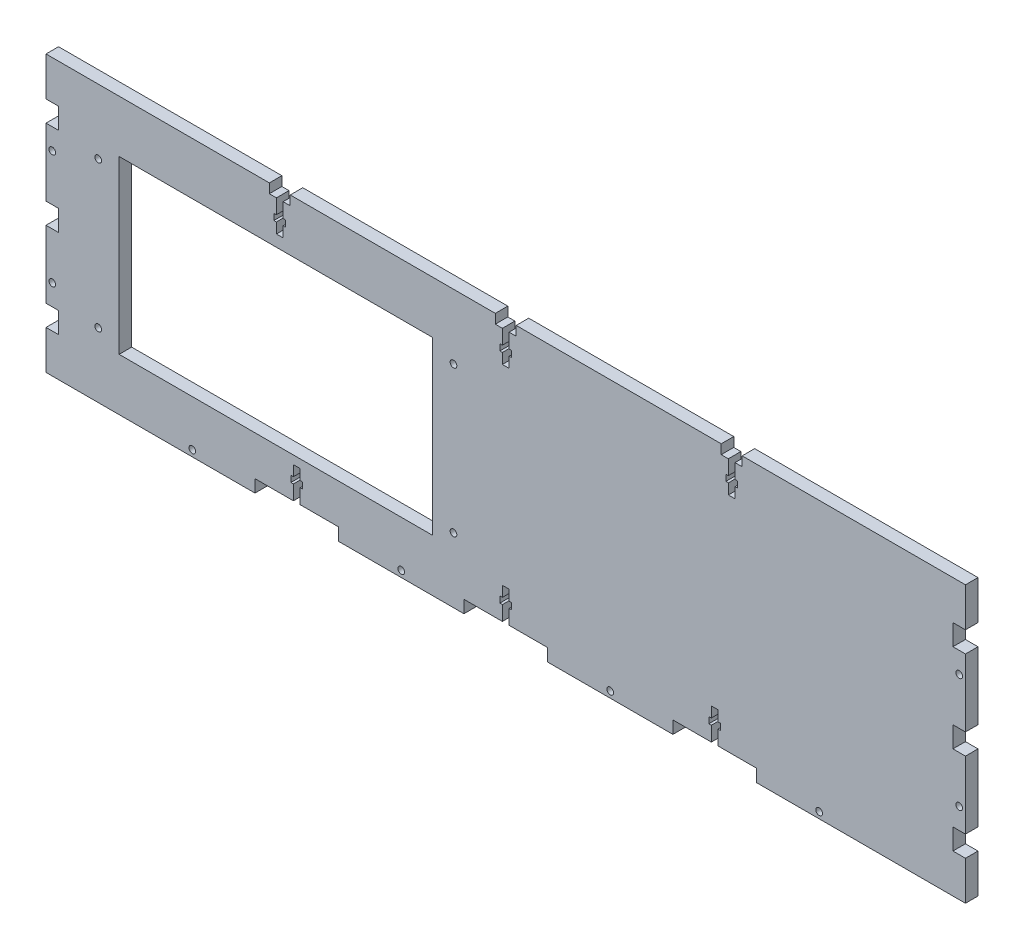
SolidWorks part; units mm, degrees
ref_plane "Front Plane" through (0, 0, 0) normal (0, 0, 1) x (1, 0, 0)
ref_plane "Top Plane" through (0, 0, 0) normal (0, 1, 0) x (1, 0, 0)
ref_plane "Right Plane" through (0, 0, 0) normal (1, 0, 0) x (0, 0, -1)
sketch "Sketch1" plane through (0, 0, 0) normal (0, 0, 1) x (1, 0, 0)
  line L1 (-220, -66) -> (220, -66)
  line L2 (-220, -66) -> (-220, 66)
  line L3 (-220, 66) -> (220, 66)
  line L4 (220, -66) -> (220, 66)
  line L5 (-220, -66) -> (220, 66) construction
  line L6 (-220, 66) -> (220, -66) construction
  point P0 (0, 0)
  dimension "D1" = 440
  dimension "D2" = 132
extrude "Boss-Extrude1" add sketch "Sketch1" along normal blind 6
sketch "Sketch2" plane through (0, 0, 0) normal (0, 0, -1) x (-1, 0, 0)
  line L0 (220, 47.3321) -> (220, 37.3321) construction
  line L1 (220, 37.3321) -> (214, 37.3321) construction
  line L2 (214, 37.3321) -> (214, 47.3321) construction
  line L3 (214, 47.3321) -> (220, 47.3321) construction
  line L12 (220, -37.3321) -> (220, -47.3321) construction
  line L13 (220, -47.3321) -> (214, -47.3321) construction
  line L14 (214, -47.3321) -> (214, -37.3321) construction
  line L15 (214, -37.3321) -> (220, -37.3321) construction
  line L16 (220, 47.3321) -> (220, 37.3321)
  line L17 (220, 37.3321) -> (214, 37.3321)
  line L18 (214, 37.3321) -> (214, 47.3321)
  line L19 (214, 47.3321) -> (220, 47.3321)
  line L20 (220, -37.3321) -> (220, -47.3321)
  line L21 (220, -47.3321) -> (214, -47.3321)
  line L22 (214, -47.3321) -> (214, -37.3321)
  line L23 (214, -37.3321) -> (220, -37.3321)
  line L24 (-214, -37.3321) -> (-214, -47.3321) construction
  line L25 (-214, -47.3321) -> (-220, -47.3321) construction
  line L26 (-220, -47.3321) -> (-220, -37.3321) construction
  line L27 (-220, -37.3321) -> (-214, -37.3321) construction
  line L28 (-214, 47.3321) -> (-214, 37.3321) construction
  line L29 (-214, 37.3321) -> (-220, 37.3321) construction
  line L30 (-220, 37.3321) -> (-220, 47.3321) construction
  line L31 (-220, 47.3321) -> (-214, 47.3321) construction
  line L32 (-214, -37.3321) -> (-214, -47.3321)
  line L33 (-214, -47.3321) -> (-220, -47.3321)
  line L34 (-220, -47.3321) -> (-220, -37.3321)
  line L35 (-220, -37.3321) -> (-214, -37.3321)
  line L36 (-214, 47.3321) -> (-214, 37.3321)
  line L37 (-214, 37.3321) -> (-220, 37.3321)
  line L38 (-220, 37.3321) -> (-220, 47.3321)
  line L39 (-220, 47.3321) -> (-214, 47.3321)
  line L44 (220, -5) -> (220, 5)
  line L45 (214, -5) -> (220, -5)
  line L46 (214, 5) -> (214, -5)
  line L47 (220, 5) -> (214, 5)
  line L48 (220, -5) -> (220, 5)
  line L49 (214, -5) -> (220, -5)
  line L50 (214, 5) -> (214, -5)
  line L51 (220, 5) -> (214, 5)
  line L52 (-214, -5) -> (-214, 5)
  line L53 (-220, -5) -> (-214, -5)
  line L54 (-220, 5) -> (-220, -5)
  line L55 (-214, 5) -> (-220, 5)
  line L56 (-214, -5) -> (-214, 5)
  line L57 (-220, -5) -> (-214, -5)
  line L58 (-220, 5) -> (-220, -5)
  line L59 (-214, 5) -> (-220, 5)
  circle A0 centre (217, 27.3321) radius 1.6 construction
  circle A1 centre (217, -27.3321) radius 1.6 construction
  circle A2 centre (-217, 27.3321) radius 1.6 construction
  circle A3 centre (-217, -27.3321) radius 1.6 construction
  circle A4 centre (217, 27.3321) radius 1.6
  circle A5 centre (217, -27.3321) radius 1.6
  circle A6 centre (-217, 27.3321) radius 1.6
  circle A7 centre (-217, -27.3321) radius 1.6
  dimension "D2" = 0
  dimension "D3" = 0
extrude "Cut-Extrude1" cut sketch "Sketch2" against normal up to next
sketch "Sketch3" plane through (0, 0, 0) normal (0, 0, -1) x (-1, 0, 0)
  circle A0 centre (-150, -63) radius 1.6 construction
  circle A1 centre (-50, -63) radius 1.6 construction
  circle A2 centre (50, -63) radius 1.6 construction
  circle A3 centre (150, -63) radius 1.6 construction
  circle A4 centre (-150, -63) radius 1.6
  circle A5 centre (-50, -63) radius 1.6
  circle A6 centre (50, -63) radius 1.6
  circle A7 centre (150, -63) radius 1.6
extrude "Cut-Extrude2" cut sketch "Sketch3" against normal up to next
sketch "Sketch4" plane through (0, 0, 0) normal (0, 0, -1) x (-1, 0, 0)
  line L0 (80, -66) -> (120, -66) construction
  line L1 (120, -66) -> (120, -60) construction
  line L2 (120, -60) -> (80, -60) construction
  line L3 (80, -60) -> (80, -66) construction
  line L4 (-20, -66) -> (20, -66) construction
  line L5 (20, -66) -> (20, -60) construction
  line L6 (20, -60) -> (-20, -60) construction
  line L7 (-20, -60) -> (-20, -66) construction
  line L8 (-120, -66) -> (-80, -66) construction
  line L9 (-80, -66) -> (-80, -60) construction
  line L10 (-80, -60) -> (-120, -60) construction
  line L11 (-120, -60) -> (-120, -66) construction
  line L12 (80, -66) -> (120, -66)
  line L13 (120, -66) -> (120, -60)
  line L14 (120, -60) -> (80, -60)
  line L15 (80, -60) -> (80, -66)
  line L16 (-20, -66) -> (20, -66)
  line L17 (20, -66) -> (20, -60)
  line L18 (20, -60) -> (-20, -60)
  line L19 (-20, -60) -> (-20, -66)
  line L20 (-120, -66) -> (-80, -66)
  line L21 (-80, -66) -> (-80, -60)
  line L22 (-80, -60) -> (-120, -60)
  line L23 (-120, -60) -> (-120, -66)
extrude "Cut-Extrude3" cut sketch "Sketch4" against normal up to next
sketch "Sketch5" plane through (0, 66, 0) normal (0, 1, 0) x (1, 0, 0)
  line L0 (220, 0) -> (-220, 0) construction
  line L1 (-113.125, -6) -> (-103.125, -6)
  line L2 (-113.125, -6) -> (-113.125, 0)
  line L3 (-113.125, 0) -> (-103.125, 0)
  line L4 (-103.125, -6) -> (-103.125, 0)
  line L5 (-113.125, -6) -> (-103.125, 0) construction
  line L6 (-113.125, 0) -> (-103.125, -6) construction
  line L7 (-103.125, -6) -> (-103.125, 0) construction
  line L8 (5, -6) -> (5, 0) construction
  line L9 (-5, -6) -> (5, -6)
  line L10 (-5, -6) -> (-5, 0)
  line L11 (-5, 0) -> (5, 0)
  line L12 (5, -6) -> (5, 0)
  line L13 (-5, -6) -> (5, 0) construction
  line L14 (-5, 0) -> (5, -6) construction
  line L15 (113.125, -6) -> (113.125, 0) construction
  line L16 (103.125, -6) -> (113.125, -6)
  line L17 (103.125, -6) -> (103.125, 0)
  line L18 (103.125, 0) -> (113.125, 0)
  line L19 (113.125, -6) -> (113.125, 0)
  line L20 (103.125, -6) -> (113.125, 0) construction
  line L21 (103.125, 0) -> (113.125, -6) construction
  point P0 (-108.125, -3)
  point P10 (0, -3)
  point P18 (108.125, -3)
extrude "Cut-Extrude4" cut sketch "Sketch5" against normal blind 4.5
sketch "Sketch6" plane through (0, 0, 0) normal (0, 0, -1) x (-1, 0, 0)
  line L0 (-108.125, 61.5) -> (-108.125, 46.5) construction
  line L1 (-113.125, 61.5) -> (-103.125, 61.5) construction
  line L2 (-109.725, 61.5) -> (-109.725, 54.5)
  line L3 (-106.525, 61.5) -> (-106.525, 54.5)
  line L4 (-109.725, 61.5) -> (-106.525, 61.5)
  line L5 (-109.725, 46.5) -> (-106.525, 46.5)
  line L6 (-106.525, 51.5) -> (-105.325, 51.5)
  line L7 (-110.925, 54.5) -> (-109.725, 54.5)
  line L8 (-110.925, 54.5) -> (-110.925, 51.5)
  line L9 (-110.925, 51.5) -> (-109.725, 51.5)
  line L10 (-105.325, 54.5) -> (-105.325, 51.5)
  line L11 (-110.925, 54.5) -> (-105.325, 51.5) construction
  line L12 (-110.925, 51.5) -> (-105.325, 54.5) construction
  line L13 (-106.525, 51.5) -> (-106.525, 46.5)
  line L14 (-106.525, 61.5) -> (-106.525, 46.5) construction
  line L15 (-109.725, 51.5) -> (-109.725, 46.5)
  line L16 (-109.725, 61.5) -> (-109.725, 46.5) construction
  line L17 (-106.525, 54.5) -> (-105.325, 54.5)
  line L18 (-1.595, 61.5) -> (-1.595, 54.5)
  line L19 (1.605, 61.5) -> (1.605, 54.5)
  line L20 (-1.595, 61.5) -> (1.605, 61.5)
  line L21 (-1.595, 46.5) -> (1.605, 46.5)
  line L22 (1.605, 51.5) -> (2.805, 51.5)
  line L23 (-2.795, 54.5) -> (-1.595, 54.5)
  line L24 (-2.795, 54.5) -> (-2.795, 51.5)
  line L25 (-2.795, 51.5) -> (-1.595, 51.5)
  line L26 (2.805, 54.5) -> (2.805, 51.5)
  line L27 (1.605, 51.5) -> (1.605, 46.5)
  line L28 (-1.595, 51.5) -> (-1.595, 46.5)
  line L29 (1.605, 54.5) -> (2.805, 54.5)
  line L30 (0.005, 61.5) -> (0.005, 46.5) construction
  line L31 (-2.795, 54.5) -> (2.805, 51.5) construction
  line L32 (-2.795, 51.5) -> (2.805, 54.5) construction
  line L33 (106.535, 61.5) -> (106.535, 54.5)
  line L34 (109.735, 61.5) -> (109.735, 54.5)
  line L35 (106.535, 61.5) -> (109.735, 61.5)
  line L36 (106.535, 46.5) -> (109.735, 46.5)
  line L37 (109.735, 51.5) -> (110.935, 51.5)
  line L38 (105.335, 54.5) -> (106.535, 54.5)
  line L39 (105.335, 54.5) -> (105.335, 51.5)
  line L40 (105.335, 51.5) -> (106.535, 51.5)
  line L41 (110.935, 54.5) -> (110.935, 51.5)
  line L42 (109.735, 51.5) -> (109.735, 46.5)
  line L43 (106.535, 51.5) -> (106.535, 46.5)
  line L44 (109.735, 54.5) -> (110.935, 54.5)
  line L45 (108.135, 61.5) -> (108.135, 46.5) construction
  line L46 (105.335, 54.5) -> (110.935, 51.5) construction
  line L47 (105.335, 51.5) -> (110.935, 54.5) construction
  line L48 (-100, -60) -> (-100, -45) construction
  line L49 (-80, -60) -> (-120, -60) construction
  line L50 (-98.4, -60) -> (-98.4, -53)
  line L51 (-101.6, -60) -> (-101.6, -53)
  line L52 (-98.4, -60) -> (-101.6, -60)
  line L53 (-98.4, -45) -> (-101.6, -45)
  line L54 (-98.4, -53) -> (-97.2, -53)
  line L55 (-102.8, -50) -> (-101.6, -50)
  line L56 (-102.8, -50) -> (-102.8, -53)
  line L57 (-102.8, -53) -> (-101.6, -53)
  line L58 (-97.2, -50) -> (-97.2, -53)
  line L59 (-102.8, -50) -> (-97.2, -53) construction
  line L60 (-102.8, -53) -> (-97.2, -50) construction
  line L61 (-98.4, -50) -> (-98.4, -45)
  line L62 (-98.4, -60) -> (-98.4, -45) construction
  line L63 (-98.4, -50) -> (-97.2, -50)
  line L64 (-101.6, -50) -> (-101.6, -45)
  line L65 (-101.6, -60) -> (-101.6, -45) construction
  line L66 (1.6, -60) -> (1.6, -53)
  line L67 (1.6, -60) -> (-1.6, -60)
  line L68 (-1.6, -60) -> (-1.6, -53)
  line L69 (-2.8, -53) -> (-1.6, -53)
  line L70 (-2.8, -50) -> (-2.8, -53)
  line L71 (-2.8, -50) -> (-1.6, -50)
  line L72 (-1.6, -50) -> (-1.6, -45)
  line L73 (1.6, -45) -> (-1.6, -45)
  line L74 (1.6, -50) -> (1.6, -45)
  line L75 (1.6, -50) -> (2.8, -50)
  line L76 (2.8, -50) -> (2.8, -53)
  line L77 (1.6, -53) -> (2.8, -53)
  line L78 (101.6, -60) -> (101.6, -53)
  line L79 (101.6, -60) -> (98.4, -60)
  line L80 (98.4, -60) -> (98.4, -53)
  line L81 (97.2, -53) -> (98.4, -53)
  line L82 (97.2, -50) -> (97.2, -53)
  line L83 (97.2, -50) -> (98.4, -50)
  line L84 (98.4, -50) -> (98.4, -45)
  line L85 (101.6, -45) -> (98.4, -45)
  line L86 (101.6, -50) -> (101.6, -45)
  line L87 (101.6, -50) -> (102.8, -50)
  line L88 (102.8, -50) -> (102.8, -53)
  line L89 (101.6, -53) -> (102.8, -53)
  point P8 (-108.125, 53)
  point P25 (0.005, 53)
  point P40 (108.135, 53)
  point P55 (-100, -51.5)
  dimension "D1" = 15
  dimension "D4" = 5.6
  dimension "D5" = 3
  dimension "D6" = 7
  dimension "D8" = 15
  dimension "D11" = 7
  dimension "D12" = 3
  dimension "D13" = 5.6
  dimension "D2" = 1.6
  dimension "D3" = 1.6
  dimension "D9" = 1.6
  dimension "D10" = 1.6
  dimension "D7" = 3
  dimension "D14" = 3
extrude "Cut-Extrude5" cut sketch "Sketch6" against normal up to next
sketch "Sketch7" plane through (0, 0, 0) normal (0, 0, -1) x (-1, 0, 0)
  line L0 (0, 0) -> (220, 0) construction
  line L1 (220, 37.3321) -> (220, 5) construction
  line L2 (113.125, 66) -> (220, 66) construction
  line L3 (35, -41) -> (185, -41)
  line L4 (35, -41) -> (35, 41)
  line L5 (35, 41) -> (185, 41)
  line L6 (185, -41) -> (185, 41)
  line L7 (35, -41) -> (185, 41) construction
  line L8 (35, 41) -> (185, -41) construction
  line L9 (25, 35) -> (25, -35) construction
  line L10 (25, 35) -> (195, 35) construction
  line L11 (25, -35) -> (35, -35) construction
  line L12 (195, -35) -> (185, -35) construction
  circle A0 centre (25, 35) radius 1.6
  circle A1 centre (25, -35) radius 1.6
  circle A2 centre (195, 35) radius 1.6
  circle A3 centre (195, -35) radius 1.6
  point P3 (110, 0)
  point P4 (110, 0)
  point P21 (110, 35)
  point P22 (25, 0)
  dimension "D5" = 3.2
  dimension "D1" = 25
  dimension "D2" = 150
  dimension "D3" = 10
  dimension "D4" = 70
extrude "Cut-Extrude6" cut sketch "Sketch7" against normal through all
equation "\"m3_depth\"=15"
equation "\"D1@Sketch6\"=\"m3_depth\""
equation "\"m3_nut_width\"=5.6"
equation "\"D4@Sketch6\"=\"m3_nut_width\""
equation "\"m3_nut_thickness\"=3"
equation "\"D5@Sketch6\"=\"m3_nut_thickness\""
equation "\"m3_nut_depth\"=7"
equation "\"D6@Sketch6\"=\"m3_nut_depth\""
